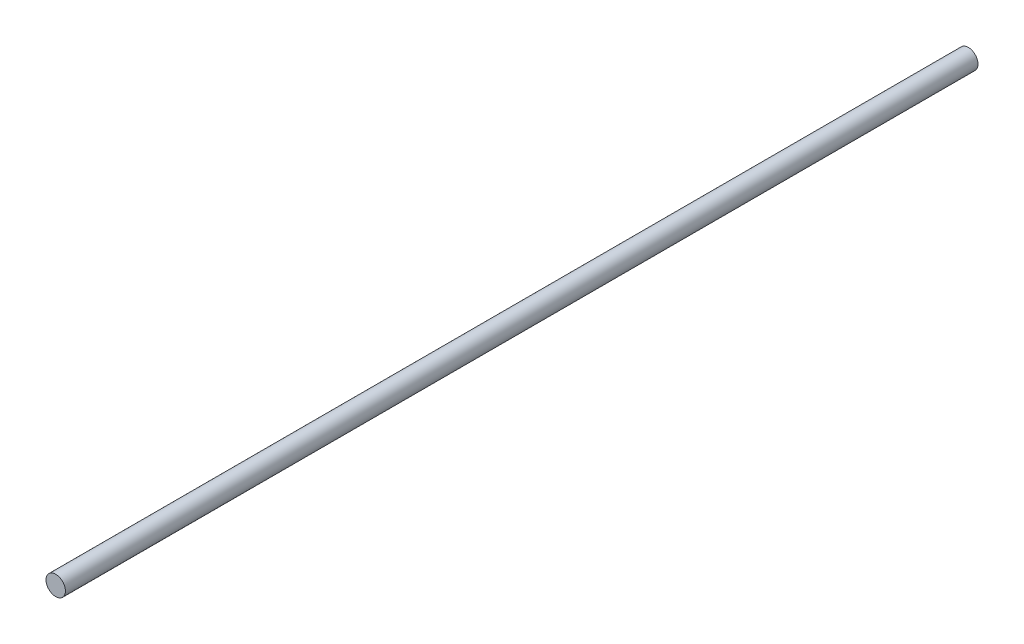
SolidWorks part; units mm, degrees
material "AISI 316 Stainless Steel Sheet (SS)"
ref_plane "Front (1)" through (0, 0, 0) normal (0, 0, 1) x (1, 0, 0)
ref_plane "Top (2)" through (0, 0, 0) normal (0, 1, 0) x (1, 0, 0)
ref_plane "Right (3)" through (0, 0, 0) normal (1, 0, 0) x (0, 0, -1)
ref_axis "X Axis" through (13.5064, 0, 0) along (-1, 0, 0)
ref_axis "Y Axis" through (0, 12.3593, 0) along (0, -1, 0)
ref_axis "Z Axis" through (0, 0, 14.1119) along (0, 0, -1)
sketch "Sketch2" plane through (0, 0, 0) normal (1, 0, 0) x (0, 0, -1)
  line L0 (12.1484, 0) -> (0, 0) construction
  line L1 (12.1484, 0) -> (387.8516, 0)
  line L2 (12.1484, 0) -> (12.1484, 4)
  line L3 (12.1484, 4) -> (387.8516, 4)
  line L4 (387.8516, 0) -> (387.8516, 4)
  line L5 (15.1484, 7.3) -> (15.1484, -7.3) construction
  line L6 (384.8516, 7.3) -> (384.8516, -7.3) construction
  dimension "D1" = 8
  dimension "D2" = 375.7032
  dimension "D3" = 3
  dimension "D4" = 3
revolve "Revolve1" add sketch "Sketch2" angle 360 about L0
cosmetic thread "Cosmetic Thread2" parameters "D2"=6.891
